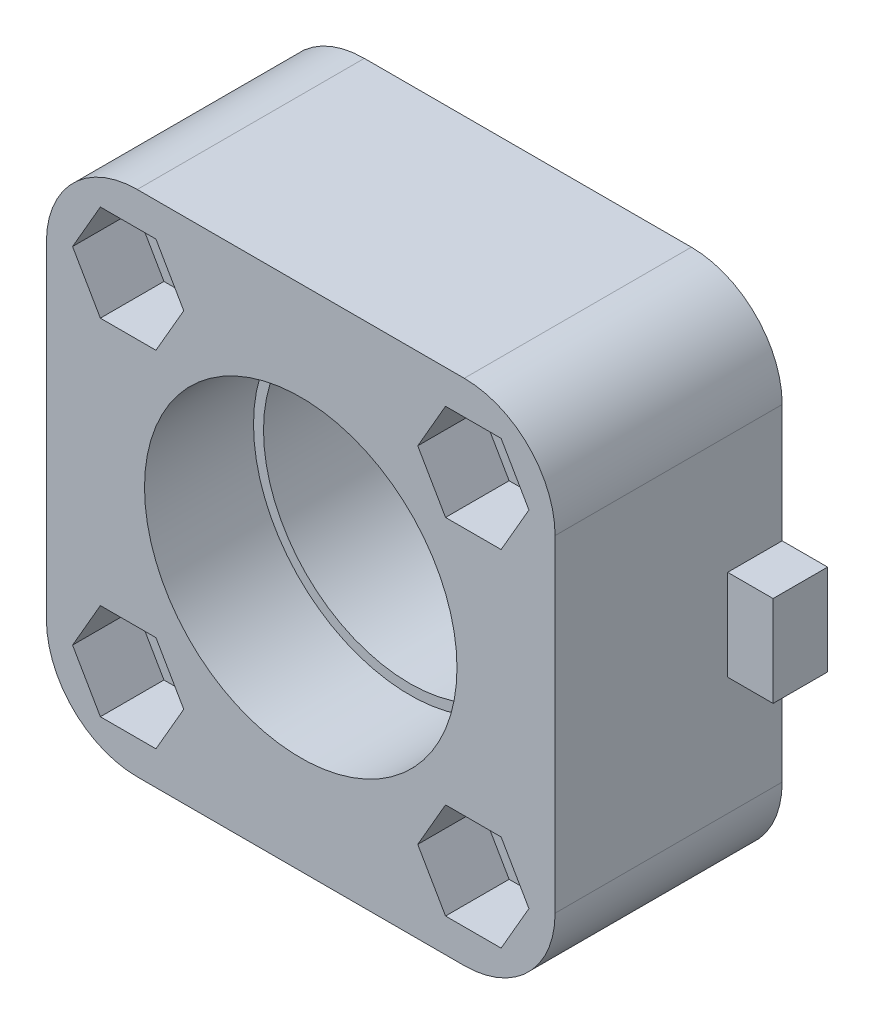
SolidWorks part; units mm, degrees
ref_plane "Alzado" through (0, 0, 0) normal (0, 0, 1) x (1, 0, 0)
ref_plane "Planta" through (0, 0, 0) normal (0, 1, 0) x (1, 0, 0)
ref_plane "Vista lateral" through (0, 0, 0) normal (1, 0, 0) x (0, 0, -1)
sketch "Croquis1" plane through (0, 0, 0) normal (0, 0, 1) x (1, 0, 0)
  line L1 (-14, -14) -> (14, -14)
  line L2 (-14, -14) -> (-14, 14)
  line L3 (-14, 14) -> (14, 14)
  line L4 (14, -14) -> (14, 14)
  line L5 (-14, -14) -> (14, 14) construction
  line L6 (-14, 14) -> (14, -14) construction
  circle A0 centre (0, 0) radius 8.05
  dimension "D1" = 16.1
  dimension "D2" = 28
  dimension "D3" = 28
extrude "Saliente-Extruir1" add sketch "Croquis1" along normal mid plane 6.5
sketch "Croquis2" plane through (0, 0, 3.25) normal (0, 0, 1) x (1, 0, 0)
  line L4 (14, -14) -> (14, 14)
  line L5 (14, 14) -> (-14, 14)
  line L6 (-14, 14) -> (-14, -14)
  line L7 (-14, -14) -> (14, -14)
  line L8 (14, -14) -> (14, 14)
  line L9 (14, 14) -> (-14, 14)
  line L10 (-14, 14) -> (-14, -14)
  line L11 (-14, -14) -> (14, -14)
  circle A0 centre (0, 0) radius 8.6
  dimension "D2" = 17.2
  dimension "D1" = 0
extrude "Saliente-Extruir2" add sketch "Croquis2" along normal blind 6
sketch "Croquis3" plane through (0, 0, 9.25) normal (0, 0, 1) x (1, 0, 0)
  line L0 (-9.5, 9.5) -> (9.5, 9.5) construction
  line L1 (9.5, 9.5) -> (9.5, -9.5) construction
  line L2 (9.5, -9.5) -> (-9.5, -9.5) construction
  line L3 (-9.5, -9.5) -> (-9.5, 9.5) construction
  line L5 (0, 13.0603) -> (0, -13.8489) construction
  line L6 (15.5492, 0) -> (-17.9148, 0) construction
  line L7 (11.03, 12.15) -> (7.97, 12.15)
  line L8 (-6.44, 9.5) -> (-7.97, 12.15)
  line L9 (-7.97, 12.15) -> (-11.03, 12.15)
  line L10 (-11.03, 12.15) -> (-12.56, 9.5)
  line L11 (-12.56, 9.5) -> (-11.03, 6.85)
  line L12 (-11.03, 6.85) -> (-7.97, 6.85)
  line L13 (-7.97, 6.85) -> (-6.44, 9.5)
  line L14 (7.97, 12.15) -> (6.44, 9.5)
  line L15 (6.44, 9.5) -> (7.97, 6.85)
  line L16 (7.97, 6.85) -> (11.03, 6.85)
  line L17 (11.03, 6.85) -> (12.56, 9.5)
  line L18 (12.56, 9.5) -> (11.03, 12.15)
  line L19 (-7.97, -6.85) -> (-11.03, -6.85)
  line L20 (-11.03, -6.85) -> (-12.56, -9.5)
  line L21 (-12.56, -9.5) -> (-11.03, -12.15)
  line L22 (-11.03, -12.15) -> (-7.97, -12.15)
  line L23 (-7.97, -12.15) -> (-6.44, -9.5)
  line L24 (-6.44, -9.5) -> (-7.97, -6.85)
  line L25 (11.03, -6.85) -> (7.97, -6.85)
  line L26 (7.97, -6.85) -> (6.44, -9.5)
  line L27 (6.44, -9.5) -> (7.97, -12.15)
  line L28 (7.97, -12.15) -> (11.03, -12.15)
  line L29 (11.03, -12.15) -> (12.56, -9.5)
  line L30 (12.56, -9.5) -> (11.03, -6.85)
  circle A0 centre (-9.5, 9.5) radius 1.5 construction
  circle A1 centre (-9.5, -9.5) radius 1.5 construction
  circle A2 centre (9.5, -9.5) radius 1.5 construction
  circle A3 centre (9.5, 9.5) radius 1.5 construction
  circle A4 centre (-9.5, 9.5) radius 2.65 construction
  circle A5 centre (9.5, 9.5) radius 2.65 construction
  circle A6 centre (-9.5, -9.5) radius 2.65 construction
  circle A7 centre (9.5, -9.5) radius 2.65 construction
  point P13 (0, -9.5)
  point P14 (-9.5, 0)
  dimension "D1" = 3
  dimension "D2" = 19
  dimension "D3" = 19
  dimension "D4" = 5.3
extrude "Cortar-Extruir1" cut sketch "Croquis3" against normal blind 3.5
sketch "Croquis6" plane through (0, 0, -3.25) normal (0, 0, -1) x (-1, 0, 0)
  line L0 (-9.5, 9.5) -> (9.5, 9.5) construction
  line L1 (9.5, 9.5) -> (9.5, -9.5) construction
  line L2 (9.5, -9.5) -> (-9.5, -9.5) construction
  line L3 (-9.5, -9.5) -> (-9.5, 9.5) construction
  line L4 (0, 17.9373) -> (0, -16.6332) construction
  line L5 (16.9599, 0) -> (-18.6245, 0) construction
  circle A0 centre (-9.5, 9.5) radius 1.5
  circle A1 centre (9.5, 9.5) radius 1.5
  circle A2 centre (9.5, -9.5) radius 1.5
  circle A3 centre (-9.5, -9.5) radius 1.5
  point P13 (0, 9.5)
  point P14 (-9.5, 0)
  dimension "D1" = 3
  dimension "D2" = 19
  dimension "D3" = 19
extrude "Cortar-Extruir2" cut sketch "Croquis6" against normal blind 23.5
sketch "Croquis7" plane through (0, 0, -3.25) normal (0, 0, -1) x (-1, 0, 0)
  line L0 (14, -14) -> (-14, -14) construction
  line L1 (-5, -14) -> (5, -14)
  line L2 (-5, -14) -> (-5, -17.5)
  line L3 (-5, -17.5) -> (5, -17.5)
  line L4 (5, -14) -> (5, -17.5)
  line L5 (-14, -14) -> (-14, 14) construction
  line L6 (-14, 2.5) -> (-16.5, 2.5)
  line L7 (-14, 2.5) -> (-14, -2.5)
  line L8 (-14, -2.5) -> (-16.5, -2.5)
  line L9 (-16.5, 2.5) -> (-16.5, -2.5)
  line L10 (14, 14) -> (14, -14) construction
  line L11 (14, 2.5) -> (16.5, 2.5)
  line L12 (14, 2.5) -> (14, -2.5)
  line L13 (14, -2.5) -> (16.5, -2.5)
  line L14 (16.5, 2.5) -> (16.5, -2.5)
  line L15 (0, 20.1506) -> (0, -30.1017) construction
  line L16 (-29.8997, 0) -> (35.1473, 0) construction
  line L17 (14, 5.5) -> (18.9, 5.5)
  line L18 (14, -2.5) -> (18.9, -2.5)
  line L19 (14, -2.5) -> (14, -5.5)
  line L20 (14, -5.5) -> (18.9, -5.5)
  line L21 (18.9, -2.5) -> (18.9, -5.5)
  line L22 (18.9, 2.5) -> (18.9, 5.5)
  line L23 (14, 2.5) -> (18.9, 2.5)
  line L24 (14, 2.5) -> (14, 5.5)
  point P23 (-16.5, 0)
  point P24 (16.5, 0)
  point P25 (0, -17.5)
  line M19 (-14, 14) -> (-14, -14)
  line M20 (-14, -14) -> (14, -14)
  line M21 (14, -14) -> (14, 14)
  dimension "D1" = 10
  dimension "D2" = 3.5
  dimension "D3" = 2.5
  dimension "D4" = 5
  dimension "D5" = 5
  dimension "D6" = 2.5
  dimension "D7" = 4.9
  dimension "D8" = 3
extrude "Saliente-Extruir3" add sketch "Croquis7" against normal blind 3 contours L11 L23 L22 L17 M21 | L14 L11 L13 M21 | L21 L18 L13 L20 M21 | L4 L2 L3 M20 | L6 L9 L8 M19 region at (-16.45, -4, -3.25) region at (0, -15.75, -3.25) region at (15.25, 0, -3.25) region at (-15.25, 0, -3.25) region at (-16.45, 4, -3.25)
fillet "Redondeo1" radius 5 4 edges at (-14, 14, 3) (-14, -14, 3) (14, -14, 3) (14, 14, 3)
